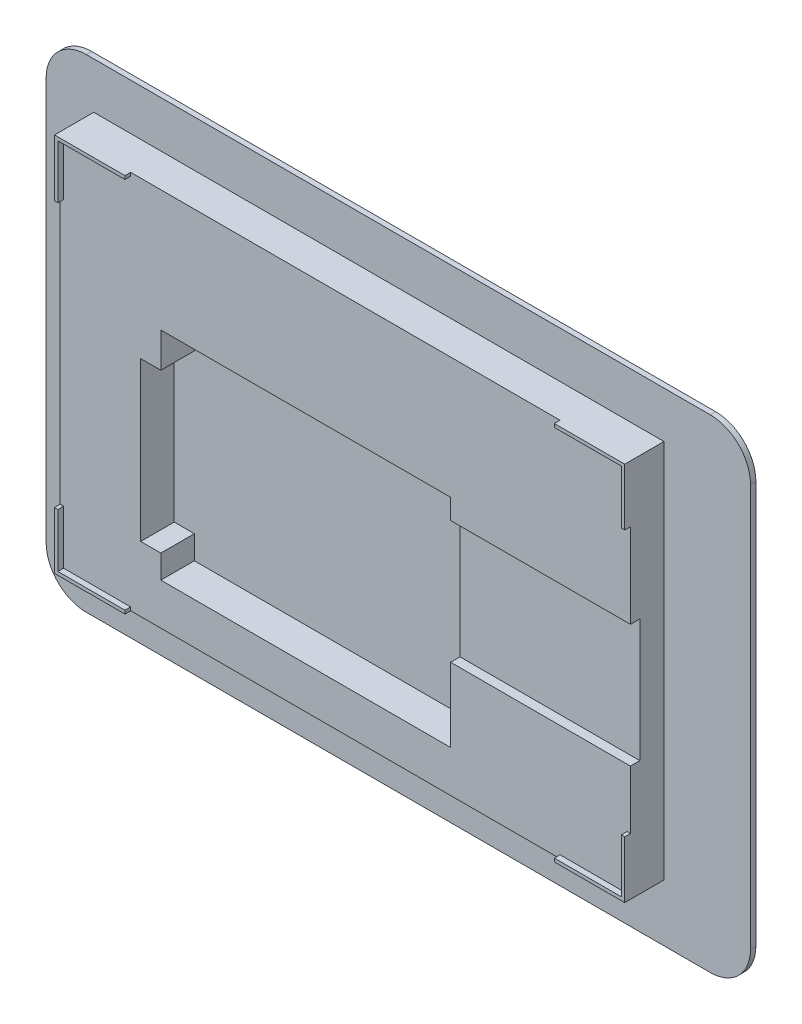
SolidWorks part; units mm, degrees
material "acero"
ref_plane "Alzado" through (0, 0, 0) normal (0, 0, 1) x (1, 0, 0)
ref_plane "Planta" through (0, 0, 0) normal (0, 1, 0) x (1, 0, 0)
ref_plane "Vista lateral" through (0, 0, 0) normal (1, 0, 0) x (0, 0, -1)
sketch "Croquis1" plane through (0, 0, 0) normal (0, 0, 1) x (1, 0, 0)
  line L0 (12, 33.3) -> (12, 9.7)
  line L1 (0, 0) -> (85, 0)
  line L2 (0, 0) -> (0, 56.6)
  line L3 (0, 56.6) -> (85, 56.6)
  line L4 (85, 0) -> (85, 56.6)
  line L5 (12, 9.7) -> (15, 9.7)
  line L6 (15, 9.7) -> (15, 6.2)
  line L7 (15, 6.2) -> (58.2, 6.2)
  line L8 (58.2, 6.2) -> (58.2, 38.5)
  line L9 (58.2, 38.5) -> (15, 38.5)
  line L10 (15, 38.5) -> (15, 33.3)
  line L11 (15, 33.3) -> (12, 33.3)
  dimension "D1" = 85
  dimension "D2" = 56.6
  dimension "D3" = 12
  dimension "D4" = 46.2
  dimension "D5" = 6.2
  dimension "D6" = 32.3
  dimension "D7" = 5.2
  dimension "D8" = 23.6
  dimension "D9" = 3
extrude "Saliente-Extruir1" add sketch "Croquis1" along normal blind 5
sketch "Croquis2" plane through (0, 0, 5) normal (0, 0, 1) x (1, 0, 0)
  line L0 (0, 56.6) -> (10.5, 56.6)
  line L1 (85, 56.6) -> (0, 56.6) construction
  line L2 (10.5, 56.6) -> (10.5, 56.1)
  line L3 (10.5, 56.1) -> (0.5, 56.1)
  line L4 (0.5, 56.1) -> (0.5, 48.1)
  line L5 (0.5, 48.1) -> (0, 48.1)
  line L6 (0, 56.6) -> (0, 0) construction
  line L7 (0, 48.1) -> (0, 56.6)
  line L8 (42.5, 56.6) -> (42.5, 0) construction
  line L9 (0, 0) -> (85, 0) construction
  line L10 (0, 28.3) -> (85, 28.3) construction
  line L11 (85, 0) -> (85, 56.6) construction
  line L12 (85, 48.1) -> (85, 56.6)
  line L13 (84.5, 48.1) -> (85, 48.1)
  line L14 (84.5, 56.1) -> (84.5, 48.1)
  line L15 (74.5, 56.1) -> (84.5, 56.1)
  line L16 (74.5, 56.6) -> (74.5, 56.1)
  line L17 (85, 56.6) -> (74.5, 56.6)
  line L18 (85, 0) -> (74.5, 0)
  line L19 (74.5, 0) -> (74.5, 0.5)
  line L20 (74.5, 0.5) -> (84.5, 0.5)
  line L21 (84.5, 0.5) -> (84.5, 8.5)
  line L22 (84.5, 8.5) -> (85, 8.5)
  line L23 (85, 8.5) -> (85, 0)
  line L24 (0, 8.5) -> (0, 0)
  line L25 (0.5, 8.5) -> (0, 8.5)
  line L26 (0.5, 0.5) -> (0.5, 8.5)
  line L27 (10.5, 0.5) -> (0.5, 0.5)
  line L28 (10.5, 0) -> (10.5, 0.5)
  line L29 (0, 0) -> (10.5, 0)
  dimension "D1" = 0.5
  dimension "D2" = 8
  dimension "D3" = 0.5
  dimension "D4" = 10
extrude "Saliente-Extruir2" add sketch "Croquis2" along normal blind 0.85
sketch "Croquis3" plane through (0, 0, 0) normal (0, 0, -1) x (-1, 0, 0)
  line L0 (-85, 56.6) -> (0, 56.6) construction
  line L1 (-84, 55.6) -> (-1, 55.6)
  line L2 (-84, 55.6) -> (-84, 1)
  line L3 (-84, 1) -> (-1, 1)
  line L4 (-1, 55.6) -> (-1, 1)
  line L5 (-85, 0) -> (-85, 56.6) construction
  line L6 (0, 56.6) -> (0, 0) construction
  line L7 (0, 0) -> (-85, 0) construction
  dimension "D1" = 1
  dimension "D2" = 1
  dimension "D3" = 1
  dimension "D4" = 1
extrude "Saliente-Extruir3" add sketch "Croquis3" along normal blind 0.9
sketch "Croquis4" plane through (0, 0, -0.9) normal (0, 0, -1) x (-1, 0, 0)
  line L1 (-91, 62.6) -> (2, 62.6)
  line L2 (-97, 56.6) -> (-97, -3.4)
  line L3 (-91, -9.4) -> (2, -9.4)
  line L4 (8, 56.6) -> (8, -3.4)
  line L5 (-85, 0) -> (-85, 56.6) construction
  line L6 (-85, 56.6) -> (0, 56.6) construction
  arc A0 (-97, -3.4) -> (-91, -9.4) centre (-91, -3.4) ccw
  arc A1 (2, -9.4) -> (8, -3.4) centre (2, -3.4) ccw
  arc A2 (8, 56.6) -> (2, 62.6) centre (2, 56.6) ccw
  arc A3 (-97, 56.6) -> (-91, 62.6) centre (-91, 56.6) cw
  dimension "D1" = 6
  dimension "D2" = 72
  dimension "D3" = 105
  dimension "D4" = 12
  dimension "D5" = 6
extrude "Saliente-Extruir4" add sketch "Croquis4" along normal blind 0.8
sketch "Croquis5" plane through (0, 0, -1.7) normal (0, 0, -1) x (-1, 0, 0)
  line L0 (-97, 56.6) -> (-97, -3.4) construction
  line L1 (-82, 51.6) -> (-7, 51.6)
  line L2 (-82, 51.6) -> (-82, 1.6)
  line L3 (-82, 1.6) -> (-7, 1.6)
  line L4 (-7, 51.6) -> (-7, 1.6)
  line L5 (8, -3.4) -> (8, 56.6) construction
  line L6 (2, 62.6) -> (-91, 62.6) construction
  line L7 (-91, -9.4) -> (2, -9.4) construction
  dimension "D1" = 15
  dimension "D2" = 15
  dimension "D3" = 11
  dimension "D4" = 11
extrude "Cortar-Extruir1" cut sketch "Croquis5" against normal blind 0.1
sketch "Croquis6" plane through (0, 0, 5) normal (0, 0, 1) x (1, 0, 0)
  line L0 (58.2, 35.5) -> (85, 35.5)
  line L1 (58.2, 6.2) -> (58.2, 38.5) construction
  line L2 (85, 8.5) -> (85, 48.1) construction
  line L3 (85, 35.5) -> (85, 17.2)
  line L4 (85, 17.2) -> (58.2, 17.2)
  line L5 (58.2, 6.2) -> (58.2, 38.5) construction
  line L6 (58.2, 17.2) -> (58.2, 35.5)
  line L7 (58.2, 38.5) -> (15, 38.5) construction
  dimension "D1" = 18.3
  dimension "D2" = 3
extrude "Cortar-Extruir2" cut sketch "Croquis6" against normal blind 1.4
sketch "Croquis7" plane through (0, 0, 0) normal (-1, 0, 0) x (0, 0, 1)
  line L0 (2.1, 49.6) -> (2.1, 7)
  line L1 (2.1, 7) -> (0, 7)
  line L2 (0, 56.6) -> (0, 0) construction
  line L3 (0, 7) -> (0, 49.6)
  line L4 (0, 49.6) -> (2.1, 49.6)
  line L5 (5.85, 56.6) -> (0, 56.6) construction
  line L6 (5.85, 0) -> (0, 0) construction
  line L7 (5, 48.1) -> (5, 8.5) construction
  dimension "D1" = 7
  dimension "D2" = 7
  dimension "D3" = 2.9
extrude "Cortar-Extruir3" cut sketch "Croquis7" against normal blind 1
fillet "Redondeo1" radius 2.9 2 edges at (0.5, 7, 2.1) (0.5, 49.6, 2.1)
sketch "Croquis8" plane through (0, 0, -0.9) normal (0, 0, 1) x (1, 0, 0)
  line L0 (1, 47.6) -> (-2.7, 47.6)
  line L1 (1, 1) -> (1, 55.6) construction
  line L2 (-2.7, 47.6) -> (-2.7, 41.1)
  line L3 (-2.7, 41.1) -> (1, 41.1)
  line L4 (1, 41.1) -> (1, 47.6)
  line L5 (1, 15.5) -> (-2.7, 15.5)
  line L6 (-2.7, 15.5) -> (-2.7, 9)
  line L7 (-2.7, 9) -> (1, 9)
  line L8 (1, 9) -> (1, 15.5)
  line L9 (0, 0) -> (85, 0) construction
  line L10 (0, 48.1) -> (0, 8.5) construction
  line L11 (85, 56.6) -> (0, 56.6) construction
  dimension "D1" = 9
  dimension "D2" = 15.5
  dimension "D3" = 2.7
  dimension "D4" = 9
  dimension "D5" = 15.5
  dimension "D6" = 2.7
extrude "Saliente-Extruir5" add sketch "Croquis8" along normal up to surface (3 mm away) up to face at (0.5, 28.3, 2.1)
fillet "Redondeo2" radius 2 2 edges at (-2.7, 12.25, 2.1) (-2.7, 44.35, 2.1)
ref_plane "Plano1" through (42.5, 0, 0) normal (-1, 0, 0) x (0, 0, 1)
ref_plane "Plano2" through (0, 28.3, 0) normal (0, -1, 0) x (-1, 0, 0)
